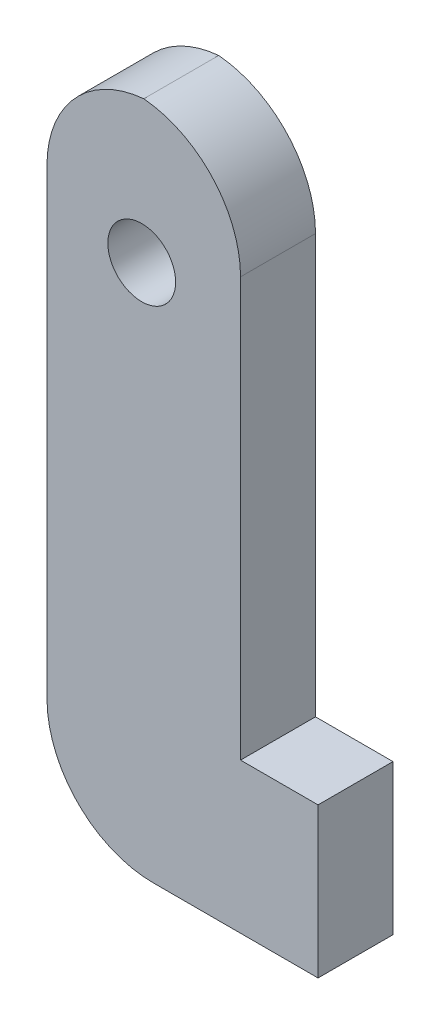
SolidWorks part; units mm, degrees
ref_plane "Front Plane" through (0, 0, 0) normal (0, 0, 1) x (1, 0, 0)
ref_plane "Top Plane" through (0, 0, 0) normal (0, 1, 0) x (1, 0, 0)
ref_plane "Right Plane" through (0, 0, 0) normal (1, 0, 0) x (0, 0, -1)
sketch "Sketch1" plane through (0, 0, 0) normal (0, 0, 1) x (1, 0, 0)
  line L1 (-38.6421, 26.9826) -> (-45.207, 26.9826)
  line L2 (-38.6421, 26.9826) -> (-38.6421, 14.2826)
  line L3 (-38.6421, 14.2826) -> (-45.207, 14.2826)
  line L7 (-45.207, 14.2826) -> (-61.6, 14.2826)
  line L8 (-45.207, 26.9826) -> (-45.207, 71.4326)
  line L9 (-45.207, 71.4326) -> (-61.6, 71.4326)
  line L10 (-61.6, 14.2826) -> (-61.6, 71.4326)
  circle A0 centre (-53.575, 59.2899) radius 2.8702
  dimension "D1" = 12.7
  dimension "D2" = 16.393
  dimension "D3" = 57.15
extrude "Boss-Extrude1" add sketch "Sketch1" along normal blind 6.35
fillet "Fillet1" radius 9 2 edges at (-45.207, 71.4326, 3.175) (-61.6, 71.4326, 3.175)
fillet "Fillet2" radius 9 1 edges at (-61.6, 14.2826, 3.175)
